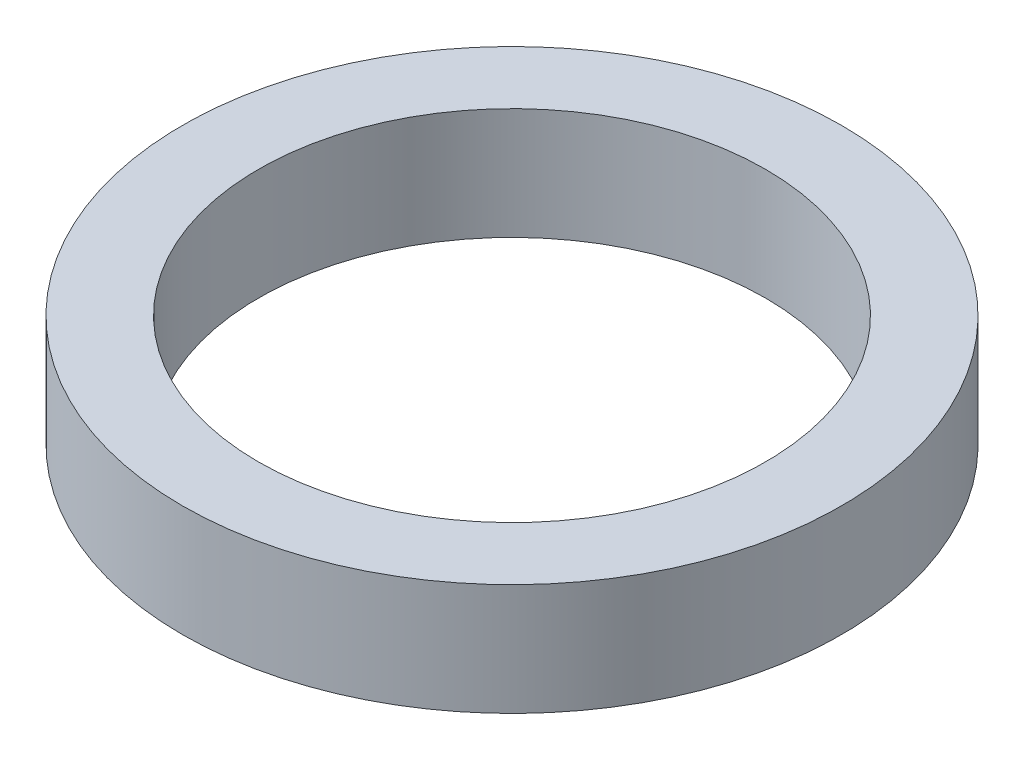
SolidWorks part; units mm, degrees
ref_plane "Front Plane" through (0, 0, 0) normal (0, 0, 1) x (1, 0, 0)
ref_plane "Top Plane" through (0, 0, 0) normal (0, 1, 0) x (1, 0, 0)
ref_plane "Right Plane" through (0, 0, 0) normal (1, 0, 0) x (0, 0, -1)
sketch "Sketch1" plane through (0, 0, 0) normal (0, 1, 0) x (1, 0, 0)
  circle A0 centre (0, 0) radius 65
  dimension "FLANGE_OD" = 130
extrude "Boss-Extrude1" add sketch "Sketch1" along normal blind 22
sketch "Sketch2" plane through (0, 0, 0) normal (0, 1, 0) x (1, 0, 0)
  circle A0 centre (0, 0) radius 50
  dimension "BORE_D" = 100
extrude "Cut-Extrude1" cut sketch "Sketch2" along normal through all
sketch "Sketch3" plane through (0, 22, 0) normal (0, 1, 0) x (1, 0, 0)
  circle A0 centre (0, 0) radius 27.9581 construction
  circle A1 centre (-27.9581, 0) radius 1.6792
  dimension "BOLT_D" = 3.3583
  dimension "BOLT_PCD" = 55.9162
extrude "Cut-Extrude2" cut sketch "Sketch3" against normal blind 20.3804 rebuild error yes
pattern_circular "CirPattern1" count 4 over 360 rebuild error yes
